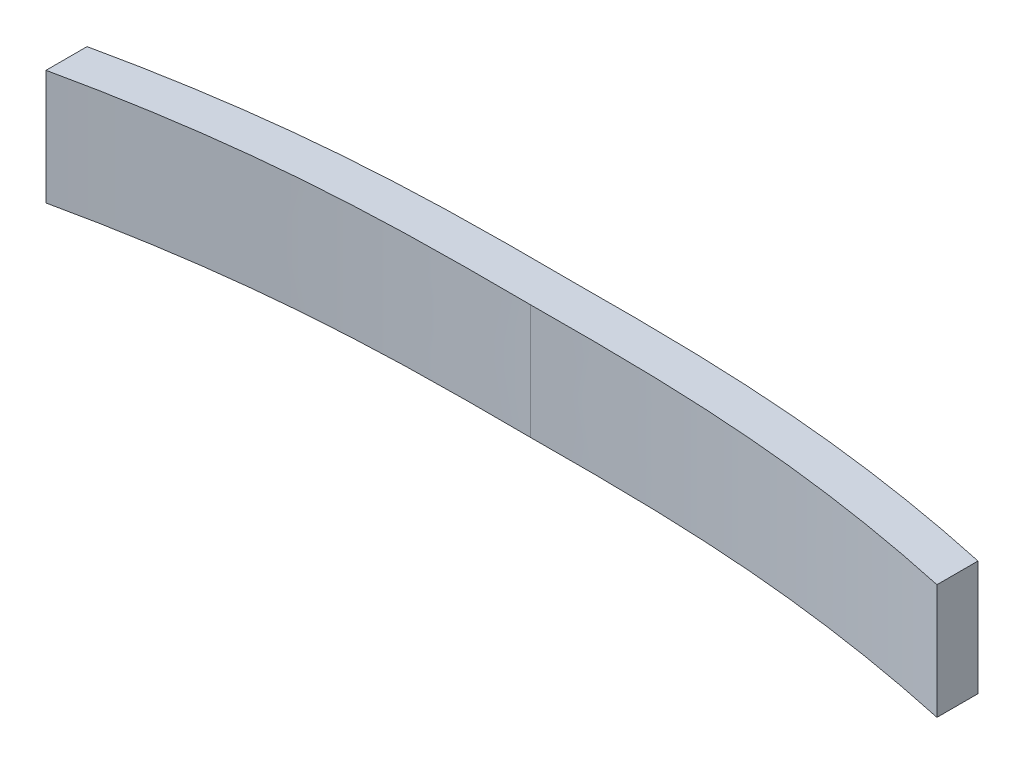
SolidWorks part; units mm, degrees
ref_plane "Front Plane" through (0, 0, 0) normal (0, 0, 1) x (1, 0, 0)
ref_plane "Top Plane" through (0, 0, 0) normal (0, 1, 0) x (1, 0, 0)
ref_plane "Right Plane" through (0, 0, 0) normal (1, 0, 0) x (0, 0, -1)
sketch "Sketch1" plane through (0, 0, 0) normal (0, 1, 0) x (1, 0, 0)
  line L0 (189.6667, 320) -> (948.3333, 320) construction
  line L1 (-903.6669, 221.9416) -> (-806.6741, 223.1267) construction
  line L2 (-2.4415, 6.8053) -> (-2.4415, 30.0052) construction
  line L3 (-115.408, 6.8053) -> (110.5249, 6.8053)
  line L4 (-115.408, 6.8053) -> (-115.408, -50.1579)
  line L5 (-115.408, -50.1579) -> (110.5249, -50.1579)
  line L6 (110.5249, 6.8053) -> (110.5249, -50.1579)
  line L7 (-2.4415, 6.8053) -> (-2.4415, -2.9496) construction
  line L8 (-56.7109, 8.0428) -> (-56.7109, -1.9572)
  line L9 (51.8279, 8.0428) -> (51.8279, -1.9572)
  line L10 (-56.7109, 10.0428) -> (-56.7109, -3.9572)
  line L11 (51.8279, -3.9572) -> (51.8279, 10.0428)
  spline S0 degree 3 poles (-56.7109, 8.0428) (-48.3237, 9.8705) (-35.0274, 11.9379) (-16.8793, 12.8603) (-7.6058, 12.8449) (-2.4415, 12.8177) knots 0 0 0 0 0.472031 0.735861 1 1 1 1
  spline S1 degree 3 poles (-56.7109, -1.9572) (-48.3237, -0.1295) (-35.0274, 1.9379) (-16.8793, 2.8603) (-7.6058, 2.8449) (-2.4415, 2.8177) knots 0 0 0 0 0.472031 0.735861 1 1 1 1
  spline S2 degree 3 poles (51.8279, -1.9572) (43.4407, -0.1295) (30.1443, 1.9379) (11.9963, 2.8603) (2.7228, 2.8449) (-2.4415, 2.8177) knots 0 0 0 0 0.472031 0.735861 1 1 1 1
  spline S3 degree 3 poles (51.8279, 8.0428) (43.4407, 9.8705) (30.1443, 11.9379) (11.9963, 12.8603) (2.7228, 12.8449) (-2.4415, 12.8177) knots 0 0 0 0 0.472031 0.735861 1 1 1 1
  spline S4 degree 3 poles (-56.7109, 10.0428) (-48.3237, 11.8705) (-35.0274, 13.9379) (-16.8793, 14.8603) (-7.6058, 14.8449) (-2.4415, 14.8177) knots 0 0 0 0 0.472031 0.735861 1 1 1 1
  spline S5 degree 3 poles (51.8279, 10.0428) (43.4407, 11.8705) (30.1443, 13.9379) (11.9963, 14.8603) (2.7228, 14.8449) (-2.4415, 14.8177) knots 0 0 0 0 0.472031 0.735861 1 1 1 1
  spline S6 degree 3 poles (-56.7109, -3.9572) (-48.3237, -2.1295) (-35.0274, -0.0621) (-16.8793, 0.8603) (-7.6058, 0.8449) (-2.4415, 0.8177) knots 0 0 0 0 0.472031 0.735861 1 1 1 1
  spline S7 degree 3 poles (51.8279, -3.9572) (43.4407, -2.1295) (30.1443, -0.0621) (11.9963, 0.8603) (2.7228, 0.8449) (-2.4415, 0.8177) knots 0 0 0 0 0.472031 0.735861 1 1 1 1
  spline S8 degree 3 poles (-56.7109, 3.0428) (-48.3237, 4.8705) (-35.0274, 6.9379) (-16.8793, 7.8603) (-7.6058, 7.8449) (-2.4415, 7.8177) knots 0 0 0 0 0.472031 0.735861 1 1 1 1
  spline S9 degree 3 poles (51.8279, 3.0428) (43.4407, 4.8705) (30.1443, 6.9379) (11.9963, 7.8603) (2.7228, 7.8449) (-2.4415, 7.8177) knots 0 0 0 0 0.472031 0.735861 1 1 1 1
  point P30 (-56.7109, 3.0428)
  dimension "D2" = 7
  dimension "D3" = 5
  dimension "D1" = 97
extrude "Boss-Extrude1" add sketch "Sketch1" along normal blind 14 contours S9 L3 L9 S3 S0 L8 S8 | L8 S8 L3 | S9 L9 L3 region at (-2.4415, 0, -9.5892) region at (-49.3361, 0, -5.6218) region at (44.4531, 0, -5.6218)
sketch "Sketch2" plane through (0, 14, 0) normal (0, 1, 0) x (1, 0, 0)
  line L0 (-55.7109, 4.2581) -> (-55.7109, 16.468)
  line L1 (-56.7109, 8.0428) -> (-56.7109, 3.0428) construction
  line L2 (-2.4415, 14.8177) -> (-2.4415, 22.16) construction
  line L3 (50.8279, 4.2581) -> (50.8279, 19.3538)
  line L4 (51.8279, 3.0428) -> (51.8279, 8.0428) construction
  line L5 (-55.7109, 16.468) -> (50.8279, 19.3538)
  spline S0 degree 3 poles (-56.7109, 4.0428) (-51.0153, 5.2834) (-42.2215, 6.8261) (-30.4783, 8.0862) (-21.9608, 8.606) (-12.6803, 8.8661) (-2.4883, 8.7888) (7.8396, 8.8667) (17.1432, 8.6046) (25.5947, 8.0817) (37.2496, 6.8392) (46.0225, 5.3073) (51.8279, 4.0428) knots 0 0 0 0 0.160114 0.245012 0.324303 0.394459 0.5 0.604256 0.678146 0.755619 0.836799 1 1 1 1
  dimension "D1" = 1
  dimension "D2" = 1
extrude "Cut-Extrude1" [suppressed] cut sketch "Sketch2" against normal blind 12 from offset 1 offset against normal yes
sketch "Sketch4" plane through (0, 14, 0) normal (0, 1, 0) x (1, 0, 0)
  spline S0 degree 3 poles (-56.7109, 10.0428) (-50.8701, 11.3153) (-42.2893, 12.8107) (-30.7314, 14.0577) (-22.3353, 14.5939) (-12.8364, 14.8675) (-2.5876, 14.7894) (7.6773, 14.8667) (17.0747, 14.6115) (25.6741, 14.0764) (37.362, 12.8198) (46.0425, 11.3031) (51.8279, 10.0428) knots 0 0 0 0 0.1642 0.239012 0.319235 0.395239 0.5 0.600749 0.677198 0.758187 0.837359 1 1 1 1
  spline S1 degree 3 poles (-56.7109, 10.0428) (-48.3237, 11.8705) (-35.0274, 13.9379) (-16.8793, 14.8603) (-7.6058, 14.8449) (-2.4415, 14.8177) knots 0 0 0 0 0.472031 0.735861 1 1 1 1 construction
  spline S2 degree 3 poles (51.8279, 10.0428) (43.4407, 11.8705) (30.1443, 13.9379) (11.9963, 14.8603) (2.7228, 14.8449) (-2.4415, 14.8177) knots 0 0 0 0 0.472031 0.735861 1 1 1 1 construction
sketch "Sketch5" [suppressed] plane through (0, 1, 0) normal (0, 1, 0) x (1, 0, 0)
  circle A0 centre (-2.4415, 14.8177) radius 2
  dimension "D1" = 0
  dimension "D2" = 0
  dimension "D3" = 4
extrude "Cut-Extrude2" [suppressed] cut sketch "Sketch5" against normal blind 10
sketch "Sketch6" [suppressed] plane through (0, 0, 0) normal (0, 0, 1) x (1, 0, 0)
  line L0 (49.8279, 1) -> (-54.7109, 1) construction
  line L1 (-59.3897, 1) -> (57.9294, 1)
  line L2 (-59.3897, 1) -> (-59.3897, -9.7624)
  line L3 (-59.3897, -9.7624) -> (57.9294, -9.7624)
  line L4 (57.9294, 1) -> (57.9294, -9.7624)
  dimension "D1" = 0
extrude "Cut-Extrude3" [suppressed] cut sketch "Sketch6" against normal through all both and the other way through all
